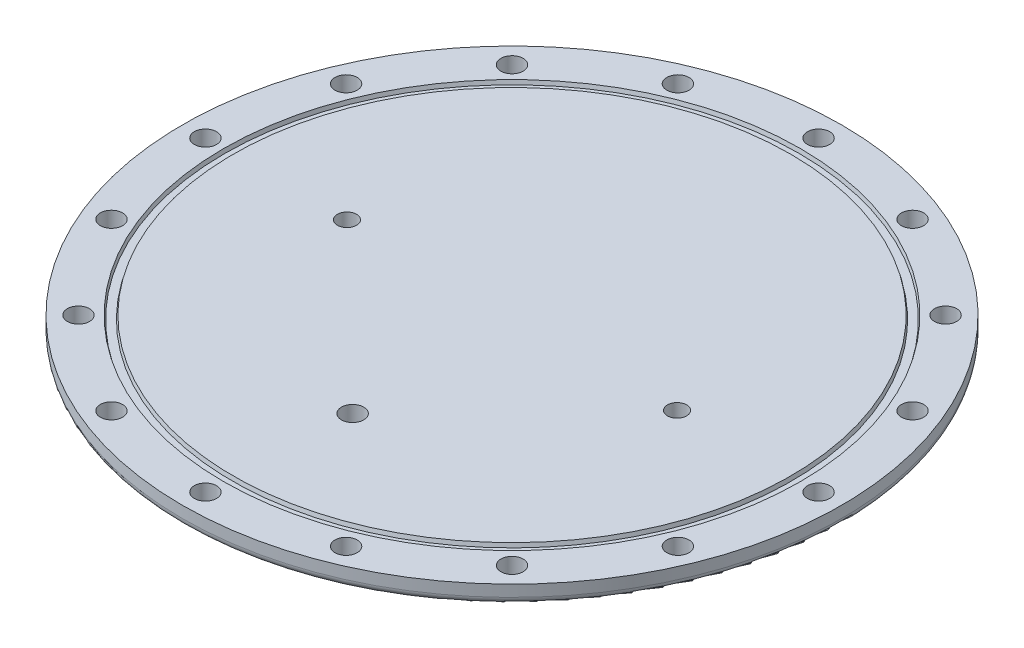
SolidWorks part; units mm, degrees
ref_plane "Front Plane" through (0, 0, 0) normal (0, 0, 1) x (1, 0, 0)
ref_plane "Top Plane" through (0, 0, 0) normal (0, 1, 0) x (1, 0, 0)
ref_plane "Right Plane" through (0, 0, 0) normal (1, 0, 0) x (0, 0, -1)
sketch "Sketch1" plane through (0, 0, 0) normal (0, 1, 0) x (1, 0, 0)
  circle A0 centre (0, 0) radius 86
  dimension "D1" = 172
extrude "Boss-Extrude1" add sketch "Sketch1" along normal blind 5 contours A0
sketch "Sketch2" plane through (0, 5, 0) normal (0, 1, 0) x (1, 0, 0)
  circle A0 centre (0, 0) radius 80 construction
  circle A1 centre (0, 80) radius 2.9
  circle A2 centre (30.6147, 73.9104) radius 2.9
  circle A3 centre (56.5685, 56.5685) radius 2.9
  circle A4 centre (73.9104, 30.6147) radius 2.9
  circle A5 centre (80, 0) radius 2.9
  circle A6 centre (73.9104, -30.6147) radius 2.9
  circle A7 centre (56.5685, -56.5685) radius 2.9
  circle A8 centre (30.6147, -73.9104) radius 2.9
  circle A9 centre (0, -80) radius 2.9
  circle A10 centre (-30.6147, -73.9104) radius 2.9
  circle A11 centre (-56.5685, -56.5685) radius 2.9
  circle A12 centre (-73.9104, -30.6147) radius 2.9
  circle A13 centre (-80, 0) radius 2.9
  circle A14 centre (-73.9104, 30.6147) radius 2.9
  circle A15 centre (-56.5685, 56.5685) radius 2.9
  circle A16 centre (-30.6147, 73.9104) radius 2.9
  point P38 (0, 0)
  dimension "D1" = 160
  dimension "D2" = 5.8
  dimension "D3" = 16
extrude "Cut-Extrude1" cut sketch "Sketch2" against normal up to next
sketch "Sketch5" plane through (0, 0, 0) normal (0, -1, 0) x (1, 0, 0)
  circle A0 centre (43.0643, 0) radius 2.5
  circle A1 centre (-43.0643, 0) radius 2.5
  circle A2 centre (0, 0) radius 43.0643 construction
  circle A3 centre (1.4467, 43.04) radius 2.9
  dimension "D1" = 5
  dimension "D2" = 5.8
extrude "Cut-Extrude2" cut sketch "Sketch5" against normal up to next
sketch "Sketch4" plane through (0, 0, 0) normal (0, 0, 1) x (1, 0, 0)
  line L0 (0, 0) -> (74, 0) construction
  line L1 (-86, 0) -> (86, 0) construction
  line L2 (74, 0) -> (74, 5) construction
  line L3 (76.8104, 5) -> (71.0104, 5) construction
  line L4 (74, 4) -> (75, 4)
  line L5 (75, 4) -> (75.2679, 5)
  line L6 (75.2679, 5) -> (72.7321, 5)
  line L7 (72.7321, 5) -> (73, 4)
  line L8 (73, 4) -> (74, 4)
  line L9 (0, 0) -> (0, 12.8224) construction
  dimension "D1" = 74
  dimension "D2" = 2
  dimension "D3" = 1
  dimension "D4" = 75
revolve "Cut-Revolve1" cut sketch "Sketch4" angle 360 about L9
fillet "Fillet1" radius 2 1 edges at (0, 0, 86)
